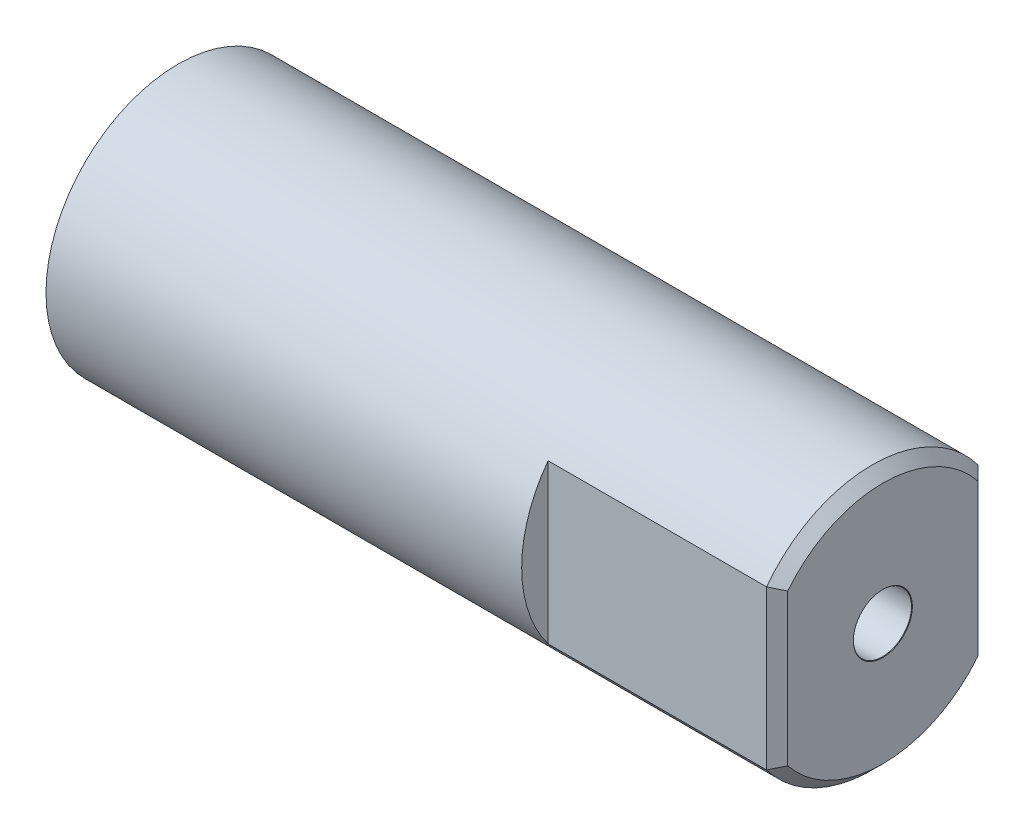
SolidWorks part; units mm, degrees
ref_plane "Front Plane" through (0, 0, 0) normal (0, 0, 1) x (1, 0, 0)
ref_plane "Top Plane" through (0, 0, 0) normal (0, 1, 0) x (1, 0, 0)
ref_plane "Right Plane" through (0, 0, 0) normal (1, 0, 0) x (0, 0, -1)
sketch "Sketch1" plane through (0, 0, 0) normal (0, 0, 1) x (1, 0, 0)
  line L0 (0, 7.5) -> (40, 7.5)
  line L1 (40, 7.5) -> (40, 0)
  line L2 (40, 0) -> (0, 0)
  line L3 (0, 0) -> (0, 7.5)
  dimension "D1" = 7.5
  dimension "D2" = 40
revolve "Revolve1" add sketch "Sketch1" angle 360 about L2
sketch "Sketch4" plane through (40, 0, 0) normal (1, 0, 0) x (0, 0, -1)
  point P0 (0, 0)
hole_wizard "Tap Drill for M4 Tap1" positions "Sketch4" profile "Sketch5" hole size "M4" standard "DIN"
sketch "Sketch5" plane through (40, 0, 0) normal (0, 1, 0) x (0, 0, -1)
  line L0 (0, 0) -> (0, 10.9914)
  line L1 (0, 10.9914) -> (1.65, 10)
  line L2 (1.65, 10) -> (1.65, 0.025)
  line L3 (1.65, 0.025) -> (1.675, 0)
  line L5 (1.675, 0) -> (0, 0)
  line L6 (-1.65, 0.025) -> (-1.675, 0) construction
  line L10 (0, 10.9914) -> (-1.65, 10) construction
  line L11 (0, -6.35) -> (0, 107.95) construction
  dimension "Hole Dia." = 3.3
  dimension "Hole Depth" = 10
  dimension "Near C'Sink Dia." = 3.35
  dimension "Near C'Sink Angle" = 90
  dimension "Drill Angle" = 118
sketch "Sketch6" plane through (40, 0, 0) normal (1, 0, 0) x (0, 0, -1)
  line L1 (-6, 4.5) -> (6, 4.5)
  line L2 (-6, 4.5) -> (-6, -4.5)
  line L3 (-6, -4.5) -> (6, -4.5)
  line L4 (6, 4.5) -> (6, -4.5)
  circle A0 centre (0, 0) radius 7.5 construction
  circle A1 centre (0, 0) radius 7.5
  circle M7 centre (0, 0) radius 7.5
  dimension "D1" = 12
extrude "Cut-Extrude1" cut sketch "Sketch6" against normal blind 13 contours L2 M7 | L4 M7 region at (40, 0, 6.6055) region at (40, 0, -6.6055)
chamfer "Chamfer1" distance 0.6 angle 45 4 edges at (40, 0, -6) (40, 7.5, 0) (40, 0, 6) (40, -7.5, 0)
